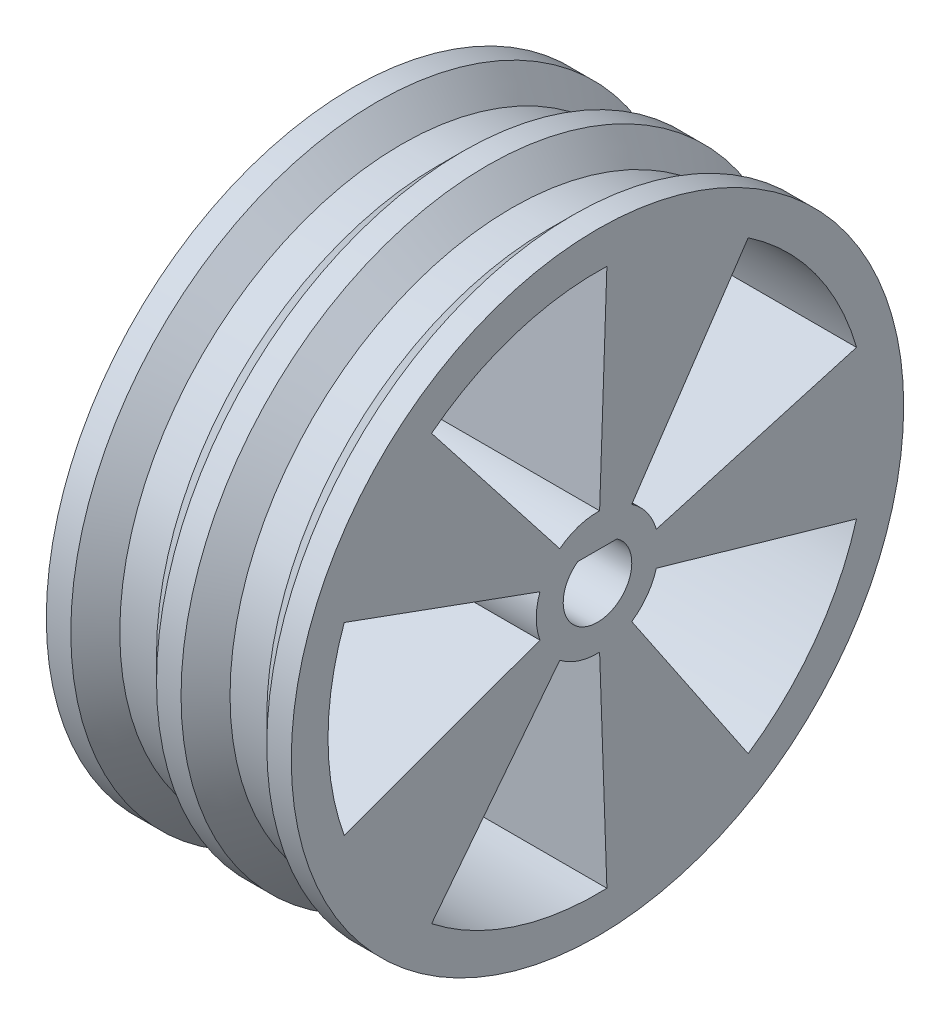
SolidWorks part; units mm, degrees
ref_plane "Plan de face" through (0, 0, 0) normal (0, 0, 1) x (1, 0, 0)
ref_plane "Plan de dessus" through (0, 0, 0) normal (0, 1, 0) x (1, 0, 0)
ref_plane "Plan de droite" through (0, 0, 0) normal (1, 0, 0) x (0, 0, -1)
sketch "Esquisse1" plane through (0, 0, 0) normal (1, 0, 0) x (0, 0, -1)
  line L0 (-1.5969, 2.3) -> (1.5969, 2.3)
  line L1 (0, 0) -> (0, 4.7784) construction
  arc A0 (-1.5969, 2.3) -> (1.5969, 2.3) centre (0, 0) ccw
  circle A1 centre (0, 0) radius 25
  point P6 (0, 2.8)
  dimension "D1" = 5.6
  dimension "D3" = 50
  dimension "D2" = 0.5
extrude "BASE" add sketch "Esquisse1" along normal blind 10 and the other way blind 10
ref_plane "PLAN GORGE" through (-8, 0, 0) normal (-1, 0, 0) x (0, 0, 1)
sketch "Esquisse2" plane through (-8, 0, 0) normal (-1, 0, 0) x (0, 0, 1)
  circle A0 centre (0, 0) radius 25
  circle A1 centre (0, 0) radius 23
  circle A5 centre (0, 0) radius 25 construction
  dimension "D1" = 2
extrude "VIDE GORGE" cut sketch "Esquisse2" against normal blind 7
mirror "SYM GORGE" about plane through (0, 0, 0) normal (1, 0, 0) of "VIDE GORGE"
sketch "Esquisse4" plane through (10, 0, 0) normal (1, 0, 0) x (0, 0, -1)
  line L0 (0, 0) -> (-22, 0) construction
  line L1 (-4.6985, 1.7101) -> (-20.6732, 7.5244)
  line L2 (-4.6985, -1.7101) -> (-20.6732, -7.5244)
  line L3 (0.1745, 4.997) -> (0.7678, 21.9866)
  line L4 (-3.0783, 3.9401) -> (-13.5446, 17.3362)
  line L5 (4.8063, 1.3782) -> (21.1478, 6.064)
  line L6 (2.796, 4.1452) -> (12.3022, 18.2388)
  line L7 (2.796, -4.1452) -> (12.3022, -18.2388)
  line L8 (4.8063, -1.3782) -> (21.1478, -6.064)
  line L9 (-3.0783, -3.9401) -> (-13.5446, -17.3362)
  line L10 (0.1745, -4.997) -> (0.7678, -21.9866)
  circle A0 centre (0, 0) radius 5
  arc A1 (-20.6732, 7.5244) -> (-20.6732, -7.5244) centre (0, 0) ccw
  circle A2 centre (0, 0) radius 25 construction
  arc A3 (0.7678, 21.9866) -> (-13.5446, 17.3362) centre (0, 0) ccw
  arc A4 (21.1478, 6.064) -> (12.3022, 18.2388) centre (0, 0) ccw
  arc A5 (12.3022, -18.2388) -> (21.1478, -6.064) centre (0, 0) ccw
  arc A6 (-13.5446, -17.3362) -> (0.7678, -21.9866) centre (0, 0) ccw
  point P30 (0, 0)
  dimension "D1" = 3
  dimension "D2" = 10
  dimension "D3" = 20
  dimension "D4" = 20
  dimension "D5" = 5
extrude "VIDE JANTE" cut sketch "Esquisse4" against normal up to surface (20 mm away) contours L0 A0 L1 A1 | A0 L0 A1 L2 | L3 A3 L4 A0 | L5 A4 L6 A0 | L7 A5 L8 A0 | L9 A6 L10 A0 region at (10, -2.6406, 14.9755) region at (10, 2.6406, 14.9755) region at (10, 14.2425, 4.6277) region at (10, -14.2425, 4.6277) region at (10, 8.8023, -12.1154) region at (10, -8.8023, -12.1154) up to face at (-10, -0.25, 0)
sketch "Esquisse6" plane through (-10, 0, 0) normal (-1, 0, 0) x (0, 0, 1)
  circle A0 centre (0, 0) radius 3
extrude "VIDE BLOC AXE" cut sketch "Esquisse6" against normal blind 4
chamfer "CHAN" distance 2 angle 45 4 edges at (-8, 0, 23) (-1, 0, 23) (1, 0, 23) (8, 0, 23)
